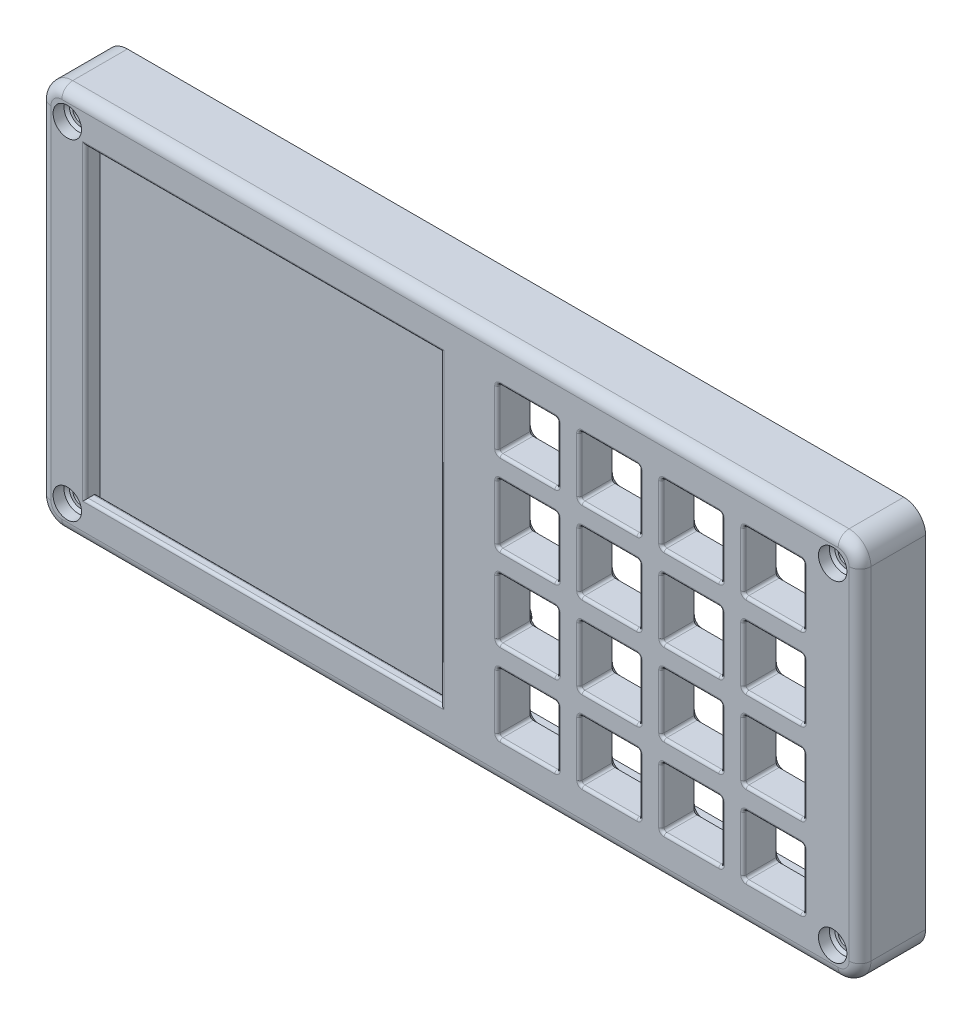
SolidWorks part; units mm, degrees
ref_plane "Front Plane" through (0, 0, 0) normal (0, 0, 1) x (1, 0, 0)
ref_plane "Top Plane" through (0, 0, 0) normal (0, 1, 0) x (1, 0, 0)
ref_plane "Right Plane" through (0, 0, 0) normal (1, 0, 0) x (0, 0, -1)
sketch "Sketch1" plane through (0, 0, 0) normal (0, 0, 1) x (1, 0, 0)
  line L1 (0, 0) -> (150, 0)
  line L2 (0, 0) -> (0, 70.49)
  line L3 (0, 70.49) -> (150, 70.49)
  line L4 (150, 0) -> (150, 70.49)
  dimension "D1" = 70.49
  dimension "D2" = 150
extrude "Boss-Extrude1" add sketch "Sketch1" along normal blind 7
sketch "Sketch2" plane through (0, 0, 7) normal (0, 0, 1) x (1, 0, 0)
  line L0 (150, 0) -> (150, 70.49) construction
  line L1 (141.68, 5.245) -> (81.68, 5.245)
  line L2 (141.68, 5.245) -> (141.68, 65.245)
  line L3 (141.68, 65.245) -> (81.68, 65.245)
  line L4 (81.68, 5.245) -> (81.68, 65.245)
  line L5 (0, 0) -> (150, 0) construction
  line L7 (128.68, 63.245) -> (139.68, 63.245)
  line L8 (128.68, 63.245) -> (128.68, 52.245)
  line L9 (128.68, 52.245) -> (139.68, 52.245)
  line L10 (139.68, 63.245) -> (139.68, 52.245)
  dimension "D1" = 60
  dimension "D2" = 60
  dimension "D3" = 8.32
  dimension "D4" = 5.245
  dimension "D5" = 11
  dimension "D6" = 11
  dimension "D7" = 2
  dimension "D8" = 2
extrude "Cut-Extrude2" cut sketch "Sketch2" against normal blind 7 contours L8 L7 L10 L9
fillet "Fillet1" radius 0.5 8 edges at (139.68, 63.245, 3.5) (139.68, 52.245, 3.5) (128.68, 52.245, 3.5) (128.68, 63.245, 3.5) (134.18, 52.245, 7) (128.68, 57.745, 7) (134.18, 63.245, 7) (139.68, 57.745, 7)
chamfer "Chamfer1" distance 1 angle 45 8 edges at (139.68, 57.745, 0) (134.18, 52.245, 0) (128.68, 57.745, 0) (128.8264, 52.3914, 0) (139.5336, 52.3914, 0) (128.8264, 63.0986, 0) (139.5336, 63.0986, 0) (134.18, 63.245, 0)
pattern_linear "LPattern1" count 4 spacing 15 along (-1, 0, 0) count 4 spacing 15 along (0, -1, 0) of "Cut-Extrude2", "Fillet1", "Chamfer1"
sketch "Sketch3" plane through (0, 0, 7) normal (0, 0, 1) x (1, 0, 0)
  line L0 (0, 70.49) -> (0, 0) construction
  line L1 (8.32, 65.245) -> (73.36, 65.245)
  line L2 (8.32, 65.245) -> (8.32, 5.245)
  line L3 (8.32, 5.245) -> (73.36, 5.245)
  line L4 (73.36, 65.245) -> (73.36, 5.245)
  line L6 (150, 0) -> (150, 70.49) construction
  line L7 (0, 0) -> (150, 0) construction
  line L8 (150, 70.49) -> (0, 70.49) construction
  dimension "D1" = 8.32
  dimension "D2" = 76.64
  dimension "D3" = 5.245
  dimension "D4" = 5.245
extrude "Cut-Extrude3" cut sketch "Sketch3" against normal blind 2.65
sketch "Sketch4" plane through (0, 65.245, 0) normal (0, -1, 0) x (-1, 0, 0)
  line L0 (-73.36, -4.35) -> (-73.36, -7) construction
  line L1 (-8.32, -7) -> (-73.36, -7)
  line L2 (-8.32, -7) -> (-8.32, -5)
  line L3 (-8.32, -5) -> (-73.36, -5)
  line L4 (-73.36, -7) -> (-73.36, -5)
  dimension "D1" = 2
extrude "Boss-Extrude2" add sketch "Sketch4" along normal blind 2
sketch "Sketch5" plane through (0, 5.245, 0) normal (0, 1, 0) x (1, 0, 0)
  line L0 (73.36, -4.35) -> (73.36, -7) construction
  line L1 (8.32, -7) -> (73.36, -7)
  line L2 (8.32, -7) -> (8.32, -5)
  line L3 (8.32, -5) -> (73.36, -5)
  line L4 (73.36, -7) -> (73.36, -5)
  dimension "D1" = 2
extrude "Boss-Extrude4" add sketch "Sketch5" along normal blind 2
fillet "Fillet3" radius 0.5 4 edges at (40.84, 7.245, 7) (73.36, 35.245, 7) (8.32, 35.245, 7) (40.84, 63.245, 7)
fillet "Fillet4" radius 0.5 2 edges at (40.84, 7.245, 5) (40.84, 63.245, 5)
fillet "Fillet5" radius 0.25 2 edges at (40.84, 65.245, 5) (40.84, 5.245, 5)
sketch "Sketch6" plane through (0, 0, 0) normal (0, 0, -1) x (-1, 0, 0)
  line L0 (0, 0) -> (-150, 0) construction
  line L1 (-2.5, 2.5) -> (-147.5, 2.5)
  line L2 (-2.5, 2.5) -> (-2.5, 67.99)
  line L3 (-2.5, 67.99) -> (-147.5, 67.99)
  line L4 (-147.5, 2.5) -> (-147.5, 67.99)
  line L5 (0, 70.49) -> (0, 0) construction
  line L6 (-150, 70.49) -> (0, 70.49) construction
  line L7 (-150, 0) -> (-150, 70.49) construction
  line L9 (0, 0) -> (-150, 0)
  line L10 (0, 0) -> (0, 70.49)
  line L11 (0, 70.49) -> (-150, 70.49)
  line L12 (-150, 0) -> (-150, 70.49)
  dimension "D1" = 2.5
  dimension "D2" = 2.5
  dimension "D3" = 2.5
  dimension "D4" = 2.5
extrude "Boss-Extrude5" add sketch "Sketch6" along normal blind 5
sketch "Sketch7" plane through (0, 0, -5) normal (0, 0, -1) x (-1, 0, 0)
  line L0 (-2.5, 2.5) -> (-2.5, 67.99) construction
  line L1 (-2.5, 52.36) -> (0, 52.36)
  line L2 (-2.5, 52.36) -> (-2.5, 40.36)
  line L3 (-2.5, 40.36) -> (0, 40.36)
  line L4 (0, 52.36) -> (0, 40.36)
  line L5 (0, 0) -> (0, 70.49) construction
  line L6 (0, 70.49) -> (-150, 70.49) construction
  dimension "D1" = 18.13
  dimension "D2" = 12
extrude "Cut-Extrude5" cut sketch "Sketch7" against normal blind 5
fillet "Fillet6" radius 1 5 edges at (0, 52.36, -2.5) (1.25, 52.36, 0) (0, 40.36, -2.5) (1.25, 40.36, 0) (0, 46.36, 0)
fillet "Fillet9" radius 4 4 edges at (150, 70.49, 1) (150, 0, 1) (0, 0, 1) (0, 70.49, 1)
fillet "Fillet10" radius 2 8 edges at (1.1716, 69.3184, 7) (148.8284, 69.3184, 7) (148.8284, 1.1716, 7) (1.1716, 1.1716, 7) (150, 35.245, 7) (75, 70.49, 7) (75, 0, 7) (0, 35.245, 7)
sketch "Sketch8" plane through (0, 0, 0) normal (0, 0, -1) x (-1, 0, 0)
  line L0 (-2.5, 52.36) -> (-2.5, 67.99) construction
  line L1 (-5.62, 52.36) -> (-2.5, 52.36)
  line L2 (-5.62, 52.36) -> (-5.62, 54.86)
  line L3 (-5.62, 54.86) -> (-2.5, 54.86)
  line L4 (-2.5, 52.36) -> (-2.5, 54.86)
  line L5 (-2.5, 40.36) -> (-5.62, 40.36)
  line L6 (-2.5, 40.36) -> (-2.5, 37.86)
  line L7 (-2.5, 37.86) -> (-5.62, 37.86)
  line L8 (-5.62, 40.36) -> (-5.62, 37.86)
  line L9 (-1, 52.36) -> (-2.5, 52.36) construction
  line L10 (-2.5, 2.5) -> (-2.5, 40.36) construction
  line L11 (-2.5, 40.36) -> (-1, 40.36) construction
  dimension "D1" = 3.12
  dimension "D2" = 2.5
  dimension "D3" = 0
  dimension "D4" = 0
  dimension "D5" = 3.12
  dimension "D6" = 2.5
  dimension "D7" = 0
  dimension "D8" = 0
extrude "Boss-Extrude6" add sketch "Sketch8" along normal blind 5
fillet "Fillet11" radius 1 2 edges at (4.06, 52.36, 0) (4.06, 40.36, 0)
fillet "Fillet12" radius 1 6 edges at (4.06, 37.86, 0) (5.62, 37.86, -2.5) (5.62, 39.61, 0) (5.62, 54.86, -2.5) (5.62, 53.11, 0) (4.06, 54.86, 0)
sketch "Sketch9" plane through (0, 0, 7) normal (0, 0, 1) x (1, 0, 0)
  line L0 (4, 70.49) -> (146, 70.49) construction
  line L1 (0, 4) -> (0, 66.49) construction
  line L2 (146, 0) -> (4, 0) construction
  line L3 (150, 66.49) -> (150, 4) construction
  circle A0 centre (5, 65.49) radius 1.5
  circle A1 centre (145, 65.49) radius 1.5
  circle A2 centre (145, 5) radius 1.5
  circle A3 centre (5, 5) radius 1.5
  dimension "D1" = 3
  dimension "D2" = 3
  dimension "D3" = 3
  dimension "D4" = 3
  dimension "D5" = 5
  dimension "D6" = 5
  dimension "D7" = 5
  dimension "D8" = 5
  dimension "D9" = 5
  dimension "D10" = 5
  dimension "D11" = 5
  dimension "D12" = 5
extrude "Cut-Extrude6" cut sketch "Sketch9" against normal blind 15
sketch "Sketch10" plane through (0, 0, 7) normal (0, 0, 1) x (1, 0, 0)
  circle A0 centre (5, 65.49) radius 2.6
  circle A1 centre (145, 65.49) radius 2.6
  circle A2 centre (145, 5) radius 2.6
  circle A3 centre (5, 5) radius 2.6
  dimension "D1" = 5.2
  dimension "D2" = 5.2
  dimension "D3" = 5.2
  dimension "D4" = 5.2
extrude "Cut-Extrude7" cut sketch "Sketch10" against normal blind 2.5
chamfer "Chamfer2" distance 0.5 angle 45 4 edges at (7.6, 5, 4.5) (147.6, 5, 4.5) (147.6, 65.49, 4.5) (7.6, 65.49, 4.5)
fillet "Fillet13" radius 1 13 edges at (2.5, 67.99, -2.5) (2.5, 2.5, -2.5) (75, 67.99, 0) (75, 2.5, 0) (2.5, 54.86, -3) (2.5, 55.1529, -0.2929) (2.5, 37.86, -3) (2.5, 37.5671, -0.2929) (2.5, 61.925, 0) (2.5, 19.68, 0) (147.5, 2.5, -2.5) (147.5, 67.99, -2.5) (147.5, 35.245, 0)
sketch "Sketch11" plane through (0, 0, 0) normal (0, 0, -1) x (-1, 0, 0)
  line L0 (0, 53.36) -> (0, 66.49) construction
  line L1 (-4, 70.49) -> (-146, 70.49) construction
  line L2 (0, 4) -> (0, 39.36) construction
  line L3 (-146, 0) -> (-4, 0) construction
  circle A0 centre (-23.56, 59.12) radius 2.25
  circle A1 centre (-22.29, 10.86) radius 2.25
  circle A2 centre (-74.36, 43.08) radius 2.25
  circle A3 centre (-74.36, 15.94) radius 2.25
  dimension "D1" = 4.5
  dimension "D2" = 4.5
  dimension "D3" = 4.5
  dimension "D4" = 4.5
  dimension "D5" = 23.56
  dimension "D6" = 11.37
  dimension "D7" = 22.29
  dimension "D8" = 10.86
  dimension "D9" = 15.94
  dimension "D10" = 74.36
  dimension "D11" = 74.36
  dimension "D12" = 27.41
extrude "Boss-Extrude7" add sketch "Sketch11" along normal blind 6.6
fillet "Fillet14" radius 0.4 4 edges at (72.11, 15.94, -6.6) (20.04, 10.86, -6.6) (72.11, 43.08, -6.6) (21.31, 59.12, -6.6)
sketch "Sketch13" plane through (0, 0, 0) normal (0, 0, -1) x (-1, 0, 0)
  circle A0 centre (-74.36, 43.08) radius 3.25
  circle A1 centre (-23.56, 59.12) radius 3.25
  circle A2 centre (-74.36, 15.94) radius 3.25
  circle A3 centre (-22.29, 10.86) radius 3.25
  circle A4 centre (-74.36, 43.08) radius 1.85 construction
  circle A5 centre (-23.56, 59.12) radius 1.85 construction
  circle A6 centre (-22.29, 10.86) radius 1.85 construction
  circle A7 centre (-74.36, 15.94) radius 1.85 construction
  dimension "D1" = 6.5
  dimension "D2" = 6.5
  dimension "D3" = 6.5
  dimension "D4" = 6.5
  dimension "D5" = 0
  dimension "D6" = 0
  dimension "D7" = 0
  dimension "D8" = 0
extrude "Boss-Extrude8" add sketch "Sketch13" along normal blind 4.8
fillet "Fillet15" radius 1 8 edges at (71.11, 15.94, 0) (19.04, 10.86, 0) (20.31, 59.12, 0) (71.11, 43.08, 0) (71.11, 15.94, -4.8) (19.04, 10.86, -4.8) (20.31, 59.12, -4.8) (71.11, 43.08, -4.8)
